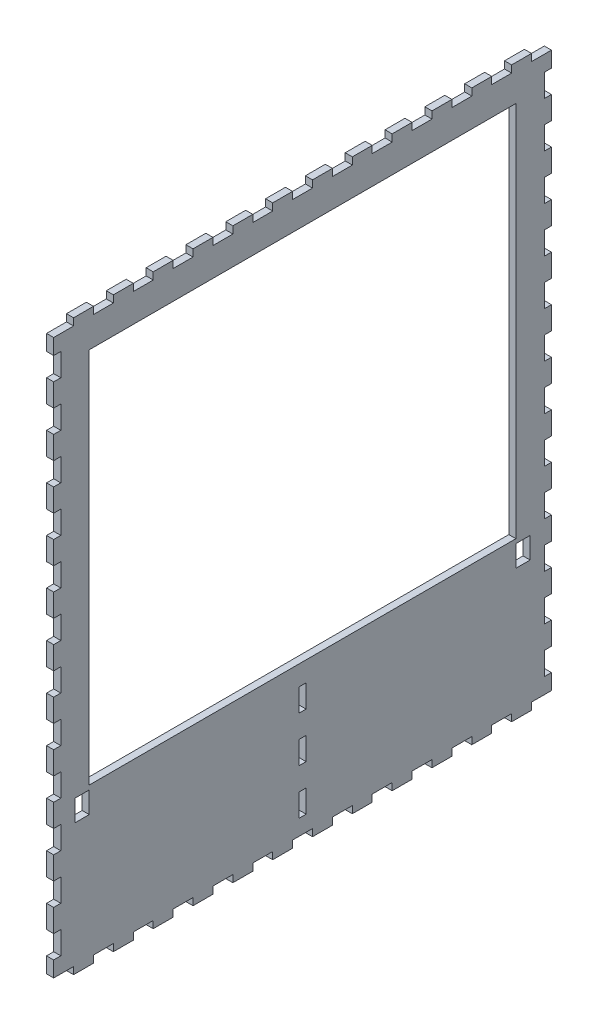
SolidWorks part; units mm, degrees
ref_plane "Plan de face" through (0, 0, 0) normal (0, 0, 1) x (1, 0, 0)
ref_plane "Plan de dessus" through (0, 0, 0) normal (0, 1, 0) x (1, 0, 0)
ref_plane "Plan de droite" through (0, 0, 0) normal (1, 0, 0) x (0, 0, -1)
sketch "Esquisse1" plane through (0, 0, 0) normal (1, 0, 0) x (0, 0, -1)
  line L1 (0, 0) -> (350, 0)
  line L2 (0, 0) -> (0, -400)
  line L3 (0, -400) -> (350, -400)
  line L4 (350, 0) -> (350, -400)
  dimension "D1" = 400
  dimension "D2" = 350
extrude "Boss.-Extru.1" add sketch "Esquisse1" along normal blind 5
sketch "Esquisse2" plane through (5, 0, 0) normal (1, 0, 0) x (0, 0, -1)
  line L0 (0, -400) -> (350, -400) construction
  line L1 (350, -400) -> (336, -400)
  line L2 (350, -400) -> (350, -395)
  line L3 (350, -395) -> (336, -395)
  line L4 (336, -400) -> (336, -395)
  dimension "D2" = 5
  dimension "D1" = 350
  dimension "D3" = 14
extrude "Enlèv. mat.-Extru.1" cut sketch "Esquisse2" against normal blind 5
ref_plane "Plan1" through (0, 0, -175) normal (0, 0, -1) x (-1, 0, 0)
ref_plane "Plan3" through (0, -200, 0) normal (0, -1, 0) x (-1, 0, 0)
pattern_linear "Répétition linéaire1" count 13 spacing 28 along (0, 0, 1) of "Enlèv. mat.-Extru.1"
mirror "Symétrie1" about plane through (0, -200, 0) normal (0, -1, 0) of "Répétition linéaire1"
sketch "Esquisse3" plane through (5, 0, 0) normal (1, 0, 0) x (0, 0, -1)
  line L0 (350, -395) -> (350, -5) construction
  line L1 (350, -384) -> (345, -384)
  line L2 (350, -384) -> (350, -368)
  line L3 (350, -368) -> (345, -368)
  line L4 (345, -384) -> (345, -368)
  line L5 (336, -400) -> (336, 0) construction
  line L6 (322, -400) -> (336, -400) construction
  dimension "D1" = 400
  dimension "D2" = 16
  dimension "D3" = 16
  dimension "D4" = 5
extrude "Enlèv. mat.-Extru.2" cut sketch "Esquisse3" against normal blind 5
pattern_linear "Répétition linéaire2" count 12 spacing 32 along (0, 1, 0) of "Enlèv. mat.-Extru.2"
mirror "Symétrie2" about plane through (0, 0, -175) normal (0, 0, -1) of "Répétition linéaire2"
sketch "Esquisse4" plane through (5, 0, 0) normal (1, 0, 0) x (0, 0, -1)
  line L0 (182, -400) -> (196, -400) construction
  line L1 (25, -25) -> (325, -25)
  line L2 (25, -25) -> (25, -290)
  line L3 (25, -290) -> (325, -290)
  line L4 (325, -25) -> (325, -290)
  line L5 (0, -128) -> (0, -144) construction
  line L6 (84, 0) -> (70, 0) construction
  line L7 (350, -48) -> (350, -32) construction
  dimension "D1" = 110
  dimension "D2" = 25
  dimension "D3" = 25
  dimension "D4" = 25
extrude "Enlèv. mat.-Extru.3" cut sketch "Esquisse4" against normal blind 5
sketch "Esquisse5" plane through (5, 0, 0) normal (1, 0, 0) x (0, 0, -1)
  line L0 (345, -304) -> (345, -320) construction
  line L1 (325, -293) -> (335, -293)
  line L2 (325, -293) -> (325, -308)
  line L3 (325, -308) -> (335, -308)
  line L4 (335, -293) -> (335, -308)
  line L5 (25, -290) -> (325, -290) construction
  dimension "D1" = 10
  dimension "D2" = 10
  dimension "D3" = 3
  dimension "D4" = 15
extrude "Enlèv. mat.-Extru.4" cut sketch "Esquisse5" against normal blind 5
mirror "Symétrie3" about plane through (0, 0, -175) normal (0, 0, -1) of "Enlèv. mat.-Extru.4"
sketch "Esquisse6" plane through (5, 0, 0) normal (1, 0, 0) x (0, 0, -1)
  line L1 (177.5, -384) -> (172.5, -384)
  line L2 (177.5, -384) -> (177.5, -368)
  line L3 (177.5, -368) -> (172.5, -368)
  line L4 (172.5, -384) -> (172.5, -368)
  line L5 (0, -352) -> (0, -368) construction
  line L7 (154, -400) -> (168, -400) construction
  line L8 (175, -368) -> (175, -384) construction
  line L9 (175, -2.75) -> (175, 2.75) construction
  dimension "D2" = 16
  dimension "D3" = 16
  dimension "D1" = 5
  dimension "D4" = 16
extrude "Enlèv. mat.-Extru.5" cut sketch "Esquisse6" against normal blind 5
pattern_linear "Répétition linéaire3" count 3 spacing 32 along (0, 1, 0) of "Enlèv. mat.-Extru.5"
equation "\"D3@Esquisse2\"=\"D1@Esquisse2\"/25"
equation "\"D2@Esquisse3\"=\"D1@Esquisse3\"/25"
equation "\"D3@Esquisse3\"=\"D2@Esquisse3\""
equation "\"D3@Esquisse4\"=\"D2@Esquisse4\""
equation "\"D4@Esquisse4\"=\"D2@Esquisse4\""
equation "\"D2@Esquisse6\"=\"D3@Esquisse6\""
equation "\"D4@Esquisse6\"=\"D2@Esquisse6\""
